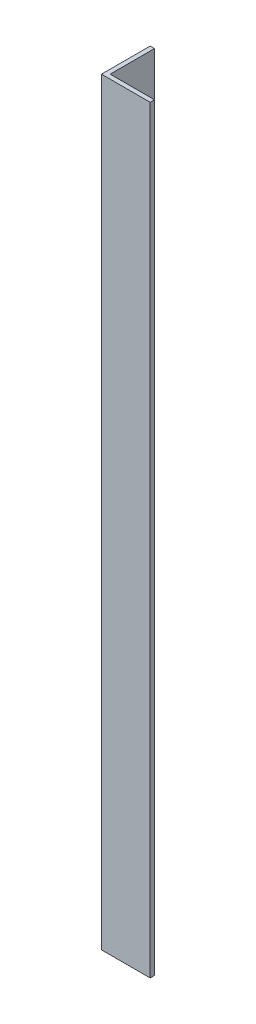
SolidWorks part; units mm, degrees
ref_plane "Спереди" through (0, 0, 0) normal (0, 0, 1) x (1, 0, 0)
ref_plane "Сверху" through (0, 0, 0) normal (0, 1, 0) x (1, 0, 0)
ref_plane "Справа" through (0, 0, 0) normal (1, 0, 0) x (0, 0, -1)
sketch "Эскиз1" plane through (0, 0, 0) normal (0, 1, 0) x (1, 0, 0)
  line L0 (0, 45) -> (0, 0)
  line L1 (0, 0) -> (45, 0)
extrude "Вытянуть-Тонкостенный1" add sketch "Эскиз1" along normal blind 700 thin thin type one direction reverse wall 4
